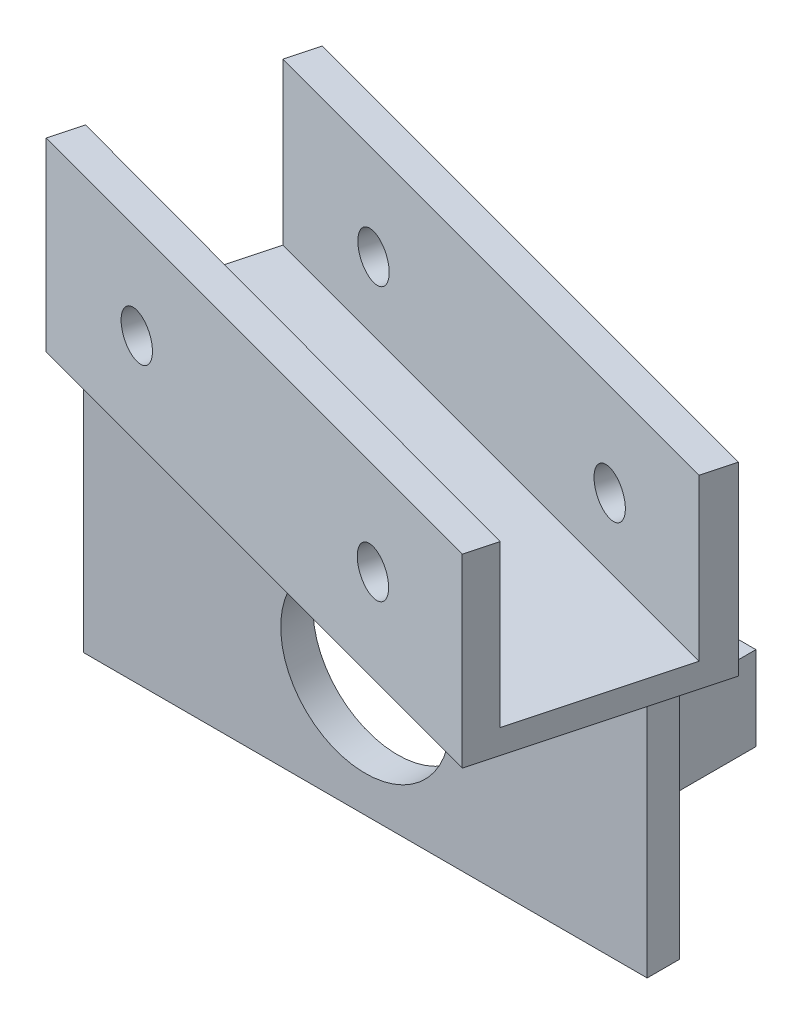
SolidWorks part; units mm, degrees
ref_plane "Front Plane" through (0, 0, 0) normal (0, 0, 1) x (1, 0, 0)
ref_plane "Top Plane" through (0, 0, 0) normal (0, 1, 0) x (1, 0, 0)
ref_plane "Right Plane" through (0, 0, 0) normal (1, 0, 0) x (0, 0, -1)
sketch "Sketch1" plane through (0, 0, 0) normal (0, 0, 1) x (1, 0, 0)
  line L1 (0, 0) -> (70, 0)
  line L2 (0, 0) -> (0, -30)
  line L3 (0, -30) -> (70, -30)
  line L4 (70, 0) -> (70, -30)
  circle A0 centre (35, -15) radius 10.5
  point P7 (70, -15)
  point P8 (35, -30)
  dimension "D1" = 21
  dimension "D2" = 30
  dimension "D3" = 70
extrude "Boss-Extrude1" add sketch "Sketch1" along normal blind 4
sketch "Sketch3" plane through (0, 0, 0) normal (0, 0, -1) x (-1, 0, 0)
  line L0 (-62.5, -8.9384) -> (-54.349, -8.9384)
  line L1 (-54.349, -8.9384) -> (-54.349, -19.3738)
  line L2 (-54.349, -19.3738) -> (-62.5, -19.3738)
  line L3 (-7.5, -5) -> (-14.3209, -5)
  line L4 (-7.5, -25) -> (-7.5, -5)
  line L5 (-62.5, -25) -> (-7.5, -25)
  line L6 (-62.5, -5) -> (-62.5, -25)
  line L7 (-7.5, -5) -> (-62.5, -5)
  line L8 (-7.5, -25) -> (-7.5, -5)
  line L10 (-62.5, -8.9384) -> (-62.5, -19.3738)
  line L12 (-14.3209, -5) -> (-14.3209, -25)
  line L13 (-14.3209, -25) -> (-7.5, -25)
  dimension "D1" = 0
extrude "Boss-Extrude2" add sketch "Sketch3" along normal blind 17
sketch "Sketch4" plane through (0, 0, -17) normal (0, 0, -1) x (-1, 0, 0)
  circle A0 centre (-58.5, -14.2891) radius 1 construction
  circle A1 centre (-58.5, -14.2891) radius 1
  circle A2 centre (-11.5, -7) radius 1 construction
  circle A3 centre (-11.5, -7) radius 1
  circle A4 centre (-11.5, -23) radius 1 construction
  circle A5 centre (-11.5, -23) radius 1
extrude "Cut-Extrude1" cut sketch "Sketch4" against normal blind 17
sketch "Sketch7" plane through (0, 0, 0) normal (0, 1, 0) x (1, 0, 0)
  line L1 (-4.6304, -4) -> (65.9508, -22.9122)
  line L2 (65.9508, -22.9122) -> (73.1977, 4.1338)
  line L5 (-4.6304, -4) -> (2.6166, 23.0459)
  line L8 (70, -4) -> (0, -4) construction
  line L9 (73.1977, 4.1338) -> (2.6166, 23.0459)
  point P4 (0, 0)
  point P10 (0, 0)
  dimension "D1" = 28
  dimension "D2" = 15
extrude "Boss-Extrude4" add sketch "Sketch7" along normal blind 3
sketch "Sketch9" plane through (0, 3, 0) normal (0, 1, 0) x (1, 0, 0)
  line L0 (-4.6304, -4) -> (65.9508, -22.9122)
  line L1 (65.9508, -22.9122) -> (66.944, -19.2056)
  line L2 (65.9508, -22.9122) -> (73.1977, 4.1338) construction
  line L3 (66.944, -19.2056) -> (-3.5951, -0.1363)
  line L4 (2.6166, 23.0459) -> (-4.6304, -4) construction
  line L5 (-3.5951, -0.1363) -> (-4.6304, -4)
  line L6 (2.6166, 23.0459) -> (1.5813, 19.1822)
  line L7 (1.5813, 19.1822) -> (72.1624, 0.2701)
  line L8 (72.1624, 0.2701) -> (73.1977, 4.1338)
  line L9 (73.1977, 4.1338) -> (2.6166, 23.0459)
  dimension "D1" = 4
  dimension "D2" = 4
extrude "Boss-Extrude5" add sketch "Sketch9" along normal blind 20
sketch "Sketch10" plane through (5.9368, 0, -22.1563) normal (0.2588, 0, -0.9659) x (-0.9659, 0, -0.2588)
  line L0 (-69.6337, 23) -> (-69.6337, 0) construction
  circle A0 centre (-53.9537, 11.5) radius 2.75
  circle A1 centre (-12.4883, 11.5) radius 2.75
  point P6 (-69.6337, 11.5)
  dimension "D1" = 5.5
  dimension "D2" = 5.5
extrude "Cut-Extrude2" cut sketch "Sketch10" against normal through all
